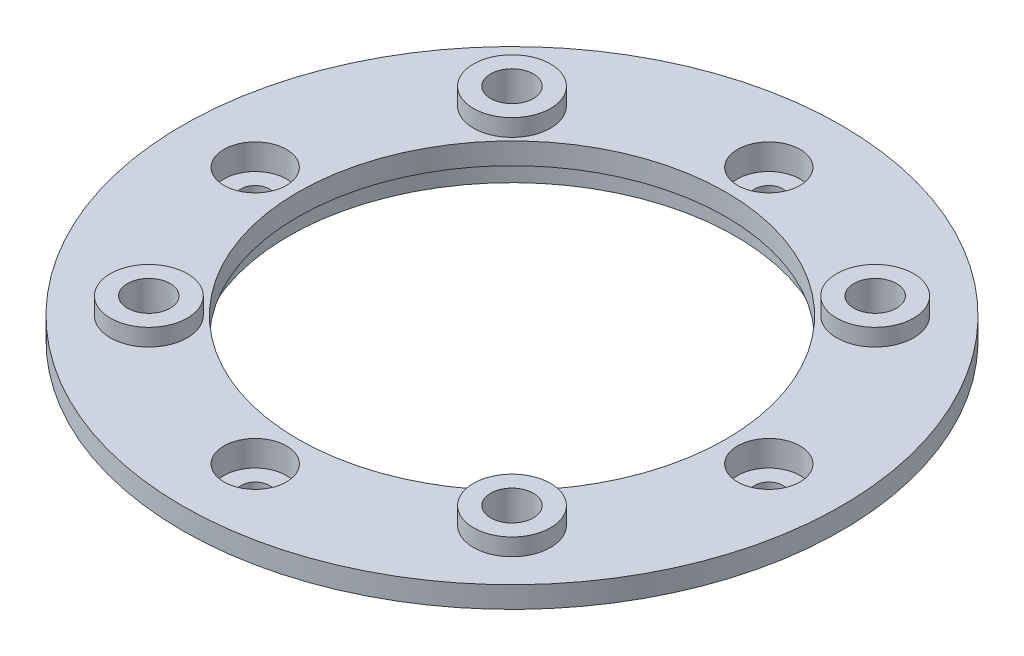
SolidWorks part; units mm, degrees
ref_plane "Front Plane" through (0, 0, 0) normal (0, 0, 1) x (1, 0, 0)
ref_plane "Top Plane" through (0, 0, 0) normal (0, 1, 0) x (1, 0, 0)
ref_plane "Right Plane" through (0, 0, 0) normal (1, 0, 0) x (0, 0, -1)
sketch "Sketch1" plane through (0, 0, 0) normal (0, 1, 0) x (1, 0, 0)
  circle A0 centre (0, 0) radius 34
  circle A1 centre (0, 0) radius 26.1
  dimension "D1" = 52.2
  dimension "D2" = 68
extrude "Boss-Extrude1" add sketch "Sketch1" along normal blind 0.5
sketch "Sketch2" plane through (0, 0.5, 0) normal (0, 1, 0) x (1, 0, 0)
  circle A0 centre (0, 0) radius 26.1 construction
  circle A1 centre (0, 0) radius 26.1
  circle A2 centre (0, 0) radius 35.5
  dimension "D1" = 71
extrude "Boss-Extrude2" add sketch "Sketch2" along normal blind 2
sketch "Sketch3" plane through (0, 2.5, 0) normal (0, 1, 0) x (1, 0, 0)
  circle A0 centre (0, 0) radius 25
  circle A3 centre (0, 0) radius 38.5
  dimension "D1" = 50
  dimension "D2" = 77
extrude "Boss-Extrude3" add sketch "Sketch3" along normal blind 2.5
chamfer "Chamfer1" distance 0.5 angle 45 1 edges at (0, 0.5, 34)
sketch "Sketch4" plane through (0, 5, 0) normal (0, 1, 0) x (1, 0, 0)
  line L0 (0, 0) -> (0, 40.8589) construction
  line L1 (0, 0) -> (33.2886, 33.2886) construction
  circle A0 centre (0, 30) radius 1.65
  circle A1 centre (21.2132, 21.2132) radius 2.5
  circle A2 centre (30, 0) radius 1.65
  circle A3 centre (21.2132, -21.2132) radius 2.5
  circle A4 centre (0, -30) radius 1.65
  circle A5 centre (-21.2132, -21.2132) radius 2.5
  circle A6 centre (-30, 0) radius 1.65
  circle A7 centre (-21.2132, 21.2132) radius 2.5
  point P23 (0, 0)
  dimension "D2" = 3.3
  dimension "D4" = 5
  dimension "D1" = 30
  dimension "D3" = 45
  dimension "D5" = 30
  dimension "D6" = 4
extrude "Cut-Extrude1" cut sketch "Sketch4" against normal through all
sketch "Sketch6" plane through (0, 5, 0) normal (0, 1, 0) x (1, 0, 0)
  circle A0 centre (0, -30) radius 1.65 construction
  circle A1 centre (30, 0) radius 1.65 construction
  circle A2 centre (0, 30) radius 1.65 construction
  circle A3 centre (-30, 0) radius 1.65 construction
  circle A4 centre (0, -30) radius 1.65
  circle A5 centre (30, 0) radius 1.65
  circle A6 centre (0, 30) radius 1.65
  circle A7 centre (-30, 0) radius 1.65
  circle A8 centre (0, -30) radius 3.65
  circle A9 centre (30, 0) radius 3.65
  circle A10 centre (0, 30) radius 3.65
  circle A11 centre (-30, 0) radius 3.65
  dimension "D1" = 2
extrude "Cut-Extrude2" cut sketch "Sketch6" against normal blind 3
sketch "Sketch7" plane through (0, 5, 0) normal (0, 1, 0) x (1, 0, 0)
  circle A0 centre (-21.2132, 21.2132) radius 4.5
  circle A1 centre (-21.2132, 21.2132) radius 2.5
  circle A2 centre (21.2132, 21.2132) radius 4.5
  circle A3 centre (21.2132, 21.2132) radius 2.5
  circle A4 centre (21.2132, -21.2132) radius 4.5
  circle A5 centre (21.2132, -21.2132) radius 2.5
  circle A6 centre (-21.2132, -21.2132) radius 4.5
  circle A7 centre (-21.2132, -21.2132) radius 2.5
  point P16 (0, 0)
  dimension "D1" = 9
  dimension "D2" = 5
  dimension "D3" = 4
extrude "Boss-Extrude4" add sketch "Sketch7" along normal blind 2
